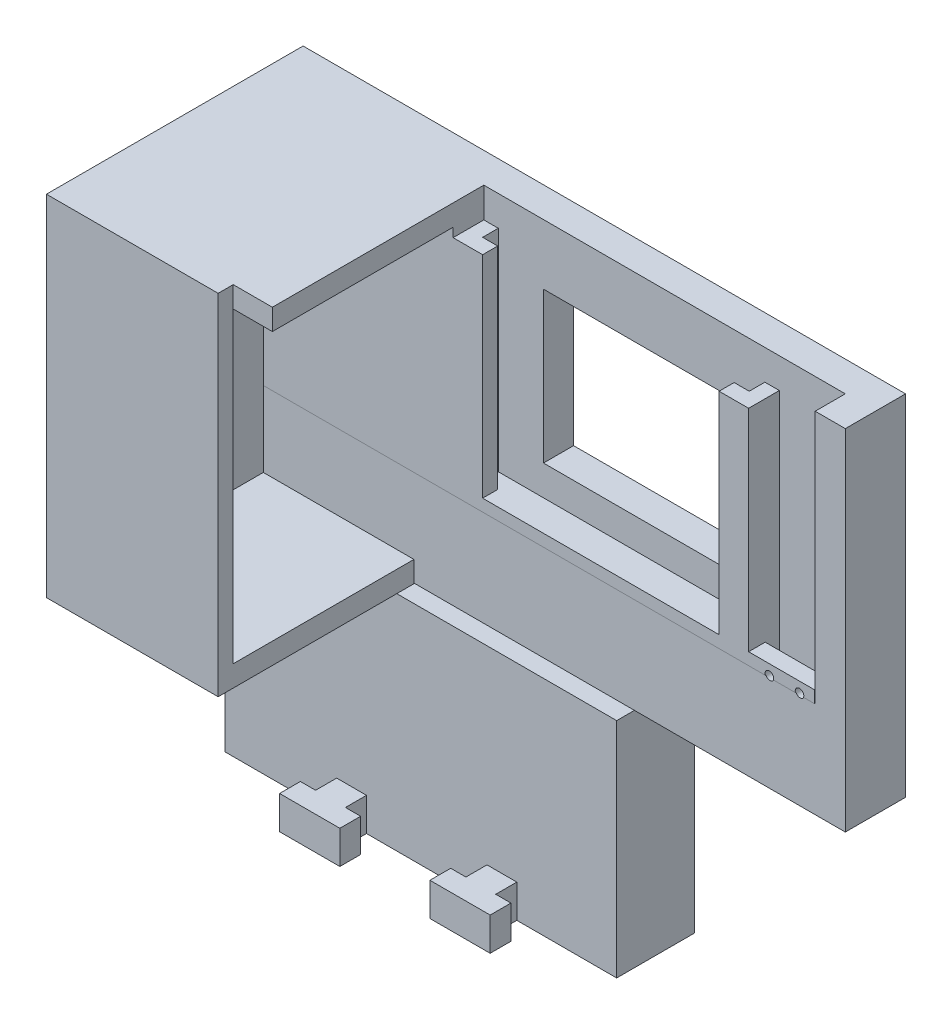
SolidWorks part; units mm, degrees
ref_plane "Front Plane" through (0, 0, 0) normal (0, 0, 1) x (1, 0, 0)
ref_plane "Top Plane" through (0, 0, 0) normal (0, 1, 0) x (1, 0, 0)
ref_plane "Right Plane" through (0, 0, 0) normal (1, 0, 0) x (0, 0, -1)
sketch "Sketch1" plane through (0, 0, 0) normal (0, 0, 1) x (1, 0, 0)
  line L1 (-95, -40) -> (95, -40)
  line L2 (-95, -40) -> (-95, 40)
  line L3 (-95, 40) -> (95, 40)
  line L4 (95, -40) -> (95, 40)
  line L5 (-95, -40) -> (95, 40) construction
  line L6 (-95, 40) -> (95, -40) construction
  point P0 (0, 0)
  dimension "D1" = 0
  dimension "D2" = 190
  dimension "80" = 80
extrude "Boss-Extrude1" add sketch "Sketch1" along normal blind 10
sketch "Sketch2" plane through (0, -40, 0) normal (0, -1, 0) x (1, 0, 0)
  line L0 (-95, 10) -> (95, 10) construction
  line L1 (-25, 10) -> (-20.2, 10)
  line L2 (-25, 10) -> (-25, 15.2)
  line L3 (-25, 15.2) -> (-20.2, 15.2)
  line L4 (-20.2, 10) -> (-20.2, 15.2)
  line L5 (-25, 20.2) -> (-15.2, 20.2)
  line L6 (-25, 20.2) -> (-25, 15.2)
  line L7 (-25, 15.2) -> (-15.2, 15.2)
  line L8 (-15.2, 20.2) -> (-15.2, 15.2)
  line L9 (73.1, 10) -> (68.3, 10)
  line L10 (73.1, 10) -> (73.1, 15.2)
  line L11 (73.1, 15.2) -> (68.3, 15.2)
  line L12 (68.3, 10) -> (68.3, 15.2)
  line L13 (63.3, 20.2) -> (73.1, 20.2)
  line L14 (63.3, 20.2) -> (63.3, 15.2)
  line L15 (63.3, 15.2) -> (73.1, 15.2)
  line L16 (73.1, 20.2) -> (73.1, 15.2)
  line L17 (-95, 10) -> (-95, 0) construction
  dimension "D1" = 0
  dimension "D2" = 0
  dimension "D3" = 0
  dimension "D4" = 5.2
  dimension "D5" = 9.8
  dimension "D6" = 5
  dimension "D7" = 4.8
  dimension "D8" = 9.8
  dimension "D9" = 5
  dimension "D10" = 0
  dimension "D11" = 0
  dimension "D12" = 0
  dimension "D13" = 5.2
  dimension "D14" = 4.8
  dimension "D15" = 88.5
  dimension "D16" = 70
extrude "Boss-Extrude2" add sketch "Sketch2" against normal blind 70 contours L8 L5 L6 L3 L7 | L16 L13 L14 L15 L11 | L4 L3 L2 L1 | L10 L11 L12 L9 region at (-20.1, -40, 17.7) region at (68.2, -40, 17.7)
sketch "Sketch3" plane through (0, 0, 10) normal (0, 0, 1) x (1, 0, 0)
  line L0 (-20.2, -40) -> (68.3, -40) construction
  line L1 (53.3, -30) -> (-5.2, -30)
  line L2 (53.3, -30) -> (53.3, 20)
  line L3 (53.3, 20) -> (-5.2, 20)
  line L4 (-5.2, -30) -> (-5.2, 20)
  line L5 (63.3, 30) -> (63.3, -40) construction
  line L6 (-15.2, 30) -> (-15.2, -40) construction
  line L7 (73.1, 30) -> (68.3, 30) construction
  dimension "D1" = 10
  dimension "D2" = 10
  dimension "D3" = 10
  dimension "D4" = 10
extrude "Cut-Extrude1" cut sketch "Sketch3" against normal blind 10
sketch "Sketch5" plane through (0, -40, 0) normal (0, -1, 0) x (-1, 0, 0)
  line L0 (25, -20.2) -> (15.2, -20.2) construction
  line L1 (95, -20.2) -> (-95, -20.2)
  line L2 (95, -20.2) -> (95, 0)
  line L3 (95, 0) -> (-95, 0)
  line L4 (-95, -20.2) -> (-95, 0)
  line L5 (95, -10) -> (95, 0) construction
  line L7 (95, 0) -> (-95, 0) construction
  line L8 (-95, -10) -> (-95, 0) construction
  dimension "D1" = 0
  dimension "D2" = 0
  dimension "D3" = 0
  dimension "D4" = 0
extrude "Boss-Extrude3" add sketch "Sketch5" along normal blind 4
sketch "Sketch6" plane through (0, 0, 0) normal (0, 0, -1) x (-1, 0, 0)
  line L0 (95, -44) -> (-95, -44) construction
  line L1 (95, -44) -> (-95, -44)
  line L2 (95, -44) -> (95, 40)
  line L3 (95, 40) -> (-95, 40)
  line L4 (-95, -44) -> (-95, 40)
  line L5 (95, -150) -> (-105, -150)
  line L6 (95, -150) -> (95, 40)
  line L7 (95, 40) -> (-105, 40)
  line L8 (-105, -150) -> (-105, 40)
  line L9 (95, 40) -> (95, -44) construction
  line L10 (-95, 40) -> (95, 40) construction
  line L11 (-95, -44) -> (-95, 40) construction
  line M5 (-95, 40) -> (-95, -44)
  line M6 (-95, -44) -> (95, -44)
  line M7 (95, -44) -> (95, 40)
  dimension "D1" = 0
  dimension "D2" = 0
  dimension "D3" = 0
  dimension "D4" = 0
  dimension "D5" = 10
  dimension "D6" = 190
  dimension "D7" = 0
  dimension "D8" = 0
extrude "Boss-Extrude5" add sketch "Sketch6" against normal blind 20 contours L8 L5 L6 L7 M7 M6 M5 region at (8.6207, -93.3793, 0)
sketch "Sketch7" plane through (0, 0, 20) normal (0, 0, 1) x (1, 0, 0)
  line L0 (105, -150) -> (105, 40) construction
  line L1 (105, -76) -> (-95, -76)
  line L2 (105, -76) -> (105, -150)
  line L3 (105, -150) -> (-95, -150)
  line L4 (-95, -76) -> (-95, -150)
  line L5 (70.7614, -89.3834) -> (70.4933, -89.3834)
  line L6 (70.7614, -89.3834) -> (70.7614, -108.9872)
  line L7 (70.7614, -108.9872) -> (70.4933, -108.9872)
  line L8 (70.4933, -89.3834) -> (70.4933, -108.9872)
  line L9 (-95, -150) -> (105, -150) construction
  line L10 (-95, -150) -> (-95, -44) construction
  line L11 (95, -44) -> (-95, -44) construction
  dimension "D1" = 0
  dimension "D2" = 0
  dimension "D3" = 0
  dimension "D4" = 32
extrude "Boss-Extrude6" add sketch "Sketch7" along normal blind 5.9
sketch "Sketch8" plane through (0, -150, 0) normal (0, -1, 0) x (1, 0, 0)
  line L0 (-95, 25.9) -> (105, 25.9) construction
  line L1 (-57.95, 32.9) -> (-48.05, 32.9)
  line L2 (-57.95, 32.9) -> (-57.95, 25.9)
  line L3 (-57.95, 25.9) -> (-48.05, 25.9)
  line L4 (-48.05, 32.9) -> (-48.05, 25.9)
  line L5 (-8.05, 32.9) -> (1.85, 32.9)
  line L6 (-8.05, 32.9) -> (-8.05, 25.9)
  line L7 (-8.05, 25.9) -> (1.85, 25.9)
  line L8 (1.85, 32.9) -> (1.85, 25.9)
  line L9 (-63, 39.8) -> (-43, 39.8)
  line L10 (-63, 39.8) -> (-63, 32.9)
  line L11 (-63, 32.9) -> (-43, 32.9)
  line L12 (-43, 39.8) -> (-43, 32.9)
  line L13 (-13.1, 39.8) -> (6.9, 39.8)
  line L14 (-13.1, 39.8) -> (-13.1, 32.9)
  line L15 (-13.1, 32.9) -> (6.9, 32.9)
  line L16 (6.9, 39.8) -> (6.9, 32.9)
  line L17 (-95, 25.9) -> (-95, 0) construction
  line M3 (105, 25.9) -> (-95, 25.9)
  dimension "D1" = 0
  dimension "D2" = 7
  dimension "D3" = 0
  dimension "D4" = 6.9
  dimension "D5" = 20
  dimension "D6" = 9.9
  dimension "D7" = 5.05
  dimension "D8" = 32
  dimension "D9" = 0
  dimension "D10" = 7
  dimension "D11" = 9.9
  dimension "D12" = 0
  dimension "D13" = 20
  dimension "D14" = 6.9
  dimension "D15" = 5.05
  dimension "D16" = 40
extrude "Boss-Extrude7" add sketch "Sketch8" against normal blind 11 contours L12 L9 L10 L11 L1 | L4 L1 L2 M3 | L16 L13 L14 L15 L5 | L8 L5 L6 M3 region at (-53, -150, 36.35) region at (-53, -150, 29.4) region at (-3.1, -150, 29.4) region at (-3.1, -150, 36.35)
sketch "Sketch21" plane through (0, -40, 0) normal (0, 1, 0) x (1, 0, 0)
  line L0 (95, -10) -> (95, -20) construction
  line L1 (95, -14.7) -> (73.1, -14.7)
  line L2 (95, -14.7) -> (95, -10)
  line L3 (95, -10) -> (73.1, -10)
  line L4 (73.1, -14.7) -> (73.1, -10)
  line L5 (73.1, -10) -> (95, -10) construction
  line L6 (73.1, -20.2) -> (73.1, -10) construction
  dimension "D1" = 0
  dimension "D2" = 0
  dimension "D3" = 4.7
  dimension "D4" = 0
extrude "Cut-Extrude7" cut sketch "Sketch21" against normal blind 5.5
sketch "Sketch22" plane through (0, 0, 20.2) normal (0, 0, 1) x (1, 0, 0)
  line L0 (95, -40) -> (73.1, -40) construction
  line L1 (95, -40) -> (95, -44) construction
  circle A0 centre (90, -43.5) radius 1.425
  circle A1 centre (80, -43.5) radius 1.425
  dimension "D1" = 2.85
  dimension "D2" = 2.85
  dimension "D4" = 3.5
  dimension "D3" = 3.5
  dimension "D5" = 5
  dimension "D6" = 10
extrude "Cut-Extrude8" cut sketch "Sketch22" against normal blind 5.5
sketch "Sketch23" plane through (0, 0, 10) normal (0, 0, 1) x (1, 0, 0)
  line L0 (-25, 30) -> (-25, -40) construction
  line L1 (-25, -40) -> (-95, -40)
  line L2 (-25, -40) -> (-25, 40)
  line L3 (-25, 40) -> (-95, 40)
  line L4 (-95, -40) -> (-95, 40)
  line L5 (-95, -40) -> (-25, -40) construction
  line L6 (-95, 40) -> (-95, -40) construction
  line L7 (95, 40) -> (-95, 40) construction
  dimension "D1" = 0
  dimension "D2" = 0
  dimension "D3" = 0
  dimension "D4" = 0
extrude "Boss-Extrude8" add sketch "Sketch23" along normal blind 10.2
sketch "Sketch24" plane through (0, 0, 25.9) normal (0, 0, 1) x (1, 0, 0)
  line L0 (105, -150) -> (105, -76) construction
  line L1 (105, -150) -> (35, -150)
  line L2 (105, -150) -> (105, -76)
  line L3 (105, -76) -> (35, -76)
  line L4 (35, -150) -> (35, -76)
  line L5 (105, -76) -> (-95, -76) construction
  line L6 (1.85, -150) -> (105, -150) construction
  dimension "D1" = 0
  dimension "D2" = 0
  dimension "D3" = 0
  dimension "D4" = 70
extrude "Cut-Extrude9" cut sketch "Sketch24" against normal through all
sketch "Sketch25" plane through (0, 0, 20.2) normal (0, 0, 1) x (1, 0, 0)
  line L0 (-25, 30) -> (-25, 40) construction
  line L1 (-25, 40) -> (-95, 40)
  line L2 (-25, 40) -> (-25, 33)
  line L3 (-25, 33) -> (-95, 33)
  line L4 (-95, 40) -> (-95, 33)
  line L5 (-88, 33) -> (-95, 33)
  line L6 (-88, 33) -> (-88, -76)
  line L7 (-88, -76) -> (-95, -76)
  line L8 (-95, 33) -> (-95, -76)
  line L9 (-25, 40) -> (-95, 40) construction
  line L10 (-95, -44) -> (-95, 40) construction
  line L11 (35, -76) -> (-95, -76) construction
  line L13 (-38, -76) -> (-88, -76)
  line L14 (-38, -76) -> (-38, -69)
  line L15 (-38, -69) -> (-88, -69)
  line L16 (-88, -76) -> (-88, -69)
  point P8 (-25, 35)
  dimension "D1" = 0
  dimension "D2" = 7
  dimension "D3" = 0
  dimension "D4" = 0
  dimension "D5" = 0
  dimension "D6" = 0
  dimension "D7" = 7
  dimension "D8" = 0
  dimension "D9" = 0
  dimension "D10" = 0
  dimension "D11" = 7
  dimension "D12" = 50
extrude "Boss-Extrude10" add sketch "Sketch25" along normal blind 60 contours L14 L15 L6 L13 | L3 L4 L1 L2 | L6 L7 L8 L5 region at (-63, -72.5, 20.2)
sketch "Sketch26" plane through (0, 0, 80.2) normal (0, 0, 1) x (1, 0, 0)
  line L0 (-38, -76) -> (-95, -76) construction
  line L1 (-38, -76) -> (-95, -76)
  line L2 (-38, -76) -> (-38, 40)
  line L3 (-38, 40) -> (-95, 40)
  line L4 (-95, -76) -> (-95, 40)
  line L5 (-38, -76) -> (-38, -69) construction
  line L6 (-95, 40) -> (-95, -76) construction
  line L7 (-25, 40) -> (-95, 40) construction
  dimension "D1" = 0
  dimension "D2" = 0
  dimension "D3" = 0
  dimension "D4" = 0
extrude "Boss-Extrude11" add sketch "Sketch26" along normal blind 5
